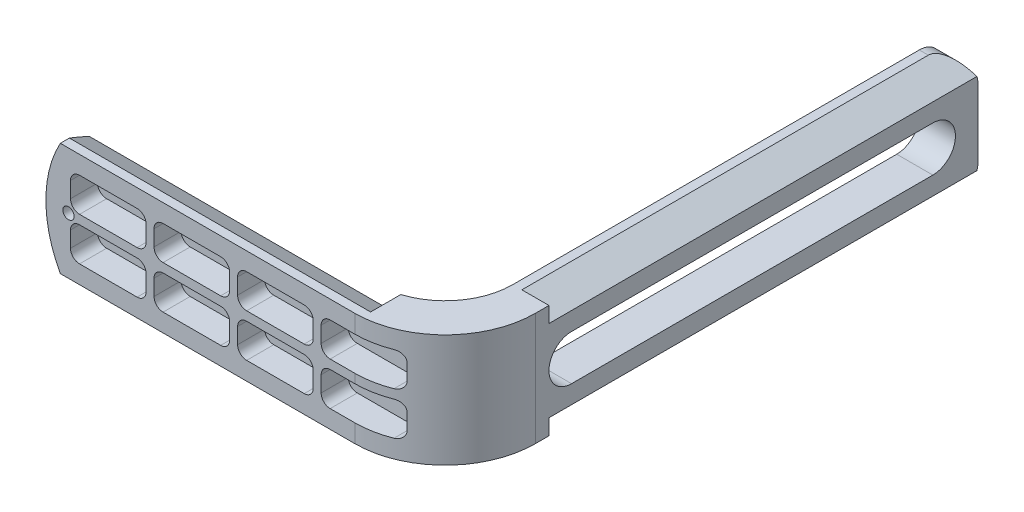
SolidWorks part; units mm, degrees
material "Сплав 2024"
ref_plane "Спереди" through (0, 0, 0) normal (0, 0, 1) x (1, 0, 0)
ref_plane "Сверху" through (0, 0, 0) normal (0, 1, 0) x (1, 0, 0)
ref_plane "Справа" through (0, 0, 0) normal (1, 0, 0) x (0, 0, -1)
sketch "Эскиз1" plane through (0, 0, 0) normal (0, 0, 1) x (1, 0, 0)
  line L1 (0, 0) -> (88.5, 0)
  line L2 (0, 0) -> (0, 25)
  line L3 (0, 25) -> (88.5, 25)
  line L4 (88.5, 0) -> (88.5, 25)
  dimension "D1" = 25
  dimension "D2" = 88.5
extrude "Бобышка-Вытянуть1" add sketch "Эскиз1" along normal blind 8
sketch "Эскиз4" plane through (0, 0, 0) normal (-1, 0, 0) x (0, 0, 1)
  line L0 (6, 0) -> (0, 3.4641)
  line L4 (0, 3.4641) -> (0, 0)
  line L5 (0, 0) -> (6, 0)
  line L6 (0, 12.5) -> (4.1286, 12.5) construction
  line L8 (0, 25) -> (6, 25)
  line L9 (0, 21.5359) -> (0, 25)
  line L11 (6, 25) -> (0, 21.5359)
  line L13 (0, 25) -> (0, 0) construction
  line L14 (8, 0) -> (0, 0) construction
  dimension "D1" = 2
  dimension "D2" = 30
extrude "Вырез-Вытянуть2" cut sketch "Эскиз4" against normal blind 70
sketch "Эскиз9" plane through (0, 0, 8) normal (0, 0, 1) x (1, 0, 0)
  line L0 (0, 12.5) -> (82.9468, 12.5) construction
  line L1 (0, 25) -> (0, 0) construction
  line L3 (5.5532, 13.5) -> (22.3032, 13.5)
  line L4 (5.5532, 13.5) -> (5.5532, 21)
  line L5 (5.5532, 21) -> (22.3032, 21)
  line L6 (22.3032, 13.5) -> (22.3032, 21)
  dimension "D1" = 7.5
  dimension "D2" = 1
  dimension "D3" = 16.75
  dimension "D4" = 5.5532
extrude "Вырез-Вытянуть3" cut sketch "Эскиз9" against normal offset from surface (6 mm away) 2 up to face at (57.125, 12.5, 0)
fillet "Скругление4" radius 2 4 edges at (5.5532, 13.5, 5) (22.3032, 13.5, 5) (22.3032, 21, 5) (5.5532, 21, 5)
pattern_linear "Линейный массив1" count 4 spacing 18.5 along (1, 0, 0) count 2 spacing 9.5 along (0, -1, 0) of "Скругление4", "Вырез-Вытянуть3"
sketch "Эскиз10" plane through (0, 0, 0) normal (0, 0, -1) x (-1, 0, 0)
  line L0 (-70, 0) -> (-88.5, 0) construction
  line L1 (-88.5, 25) -> (-80.5, 25)
  line L2 (-88.5, 25) -> (-88.5, 0)
  line L3 (-88.5, 0) -> (-80.5, 0)
  line L4 (-80.5, 25) -> (-80.5, 0)
  dimension "D1" = 8
extrude "Бобышка-Вытянуть2" add sketch "Эскиз10" along normal blind 110
fillet "Скругление5" radius 20 1 edges at (88.5, 12.5, 8)
fillet "Скругление6" radius 15 1 edges
fillet "Скругление7" radius 5 2 edges at (84.5, 0, -110) (84.5, 25, -110)
sketch "Эскиз11" plane through (0, 0, -110) normal (0, 0, -1) x (-1, 0, 0)
  line L0 (-82.5, 25) -> (-88.5, 25)
  line L2 (-88.5, 25) -> (-88.5, 21.5359)
  line L3 (-88.5, 20) -> (-88.5, 5) construction
  line L4 (-88.5, 21.5359) -> (-82.5, 25)
  line L5 (-80.5, 0) -> (-80.5, 25) construction
  line L6 (-80.5, 12.5) -> (-82.7763, 12.5) construction
  line L7 (-80.5, 5) -> (-80.5, 20) construction
  line L8 (-88.5, 3.4641) -> (-82.5, 0)
  line L9 (-88.5, 0) -> (-88.5, 3.4641)
  line L10 (-82.5, 0) -> (-88.5, 0)
  line L11 (-88.5, 25) -> (-88.5, 20) construction
  dimension "D1" = 2
  dimension "D2" = 30
extrude "Вырез-Вытянуть4" cut sketch "Эскиз11" against normal blind 95
sketch "Эскиз12" plane through (88.5, 0, 0) normal (1, 0, 0) x (0, 0, -1)
  line L0 (110, 12.5) -> (7.3499, 12.5) construction
  line L1 (110, 20) -> (110, 5) construction
  line L2 (20, 12.5) -> (100, 12.5) construction
  line L3 (20, 17.5) -> (100, 17.5)
  line L4 (20, 7.5) -> (100, 7.5)
  arc A0 (20, 17.5) -> (20, 7.5) centre (20, 12.5) ccw
  arc A1 (100, 7.5) -> (100, 17.5) centre (100, 12.5) ccw
  point P6 (60, 12.5)
  dimension "D1" = 10
  dimension "D2" = 80
  dimension "D3" = 10
extrude "Вырез-Вытянуть5" cut sketch "Эскиз12" against normal up to next
sketch "Эскиз13" plane through (0, 0, 0) normal (0, 0, -1) x (-1, 0, 0)
  line L0 (0, 12.5) -> (-5.3037, 12.5) construction
  line L1 (0, 21.5359) -> (0, 3.4641) construction
  line L2 (-3.302, 25) -> (0, 25)
  line L4 (0, 25) -> (0, 0)
  line L5 (0, 0) -> (-3.302, 0)
  line L6 (0, 0) -> (-88.5, 0) construction
  line L7 (-70, 25) -> (0, 25) construction
  arc A0 (-3.302, 0) -> (-3.302, 25) centre (-26.1, 12.5) ccw
  dimension "D1" = 52
  dimension "D2" = 26.1
extrude "Вырез-Вытянуть7" cut sketch "Эскиз13" against normal up to next
sketch "Эскиз14" plane through (0, 0, 8) normal (0, 0, 1) x (1, 0, 0)
  line L0 (0.1, 12.5) -> (5.1, 12.5) construction
  arc A0 (3.302, 25) -> (3.302, 0) centre (26.1, 12.5) ccw construction
  dimension "D1" = 5
hole_wizard "Отверстие обработанное метчиком M3x0.51" positions "Эскиз16" profile "Эскиз15" tap size "M3x0.5" standard "Ansi Metric"
sketch "Эскиз16" plane through (0, 0, 8) normal (0, 0, 1) x (1, 0, 0)
  point P0 (5.1, 12.5)
sketch "Эскиз15" plane through (5.1, 12.5, 8) normal (1, 0, 0) x (0, -1, 0)
  line L0 (0, 0) -> (0, 6.7511)
  line L1 (0, 6.7511) -> (1.25, 6)
  line L2 (1.25, 6) -> (1.25, 0)
  line L5 (1.25, 0) -> (0, 0)
  line L10 (0, 6.7511) -> (-1.25, 6) construction
  line L11 (0, -6.35) -> (0, 107.95) construction
  dimension "Диаметр сверла" = 2.5
  dimension "Глубина сверла" = 6
  dimension "Угол заточки сверла" = 118
cosmetic thread "Отверстие резьбы1" parameters "D1"=6, "D2"=3
